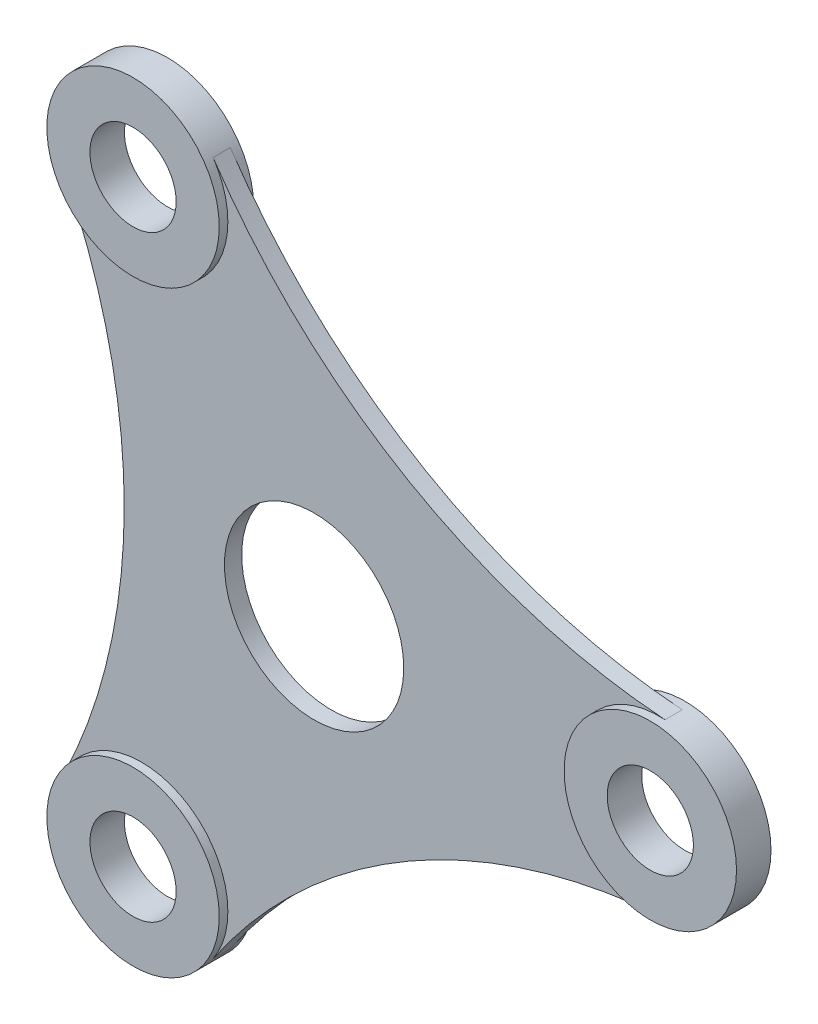
SolidWorks part; units mm, degrees
ref_plane "Front Plane" through (0, 0, 0) normal (0, 0, 1) x (1, 0, 0)
ref_plane "Top Plane" through (0, 0, 0) normal (0, 1, 0) x (1, 0, 0)
ref_plane "Right Plane" through (0, 0, 0) normal (1, 0, 0) x (0, 0, -1)
sketch "Sketch1" plane through (0, 0, 0) normal (0, 0, 1) x (1, 0, 0)
  circle A0 centre (0, 0) radius 200 construction
  circle A1 centre (0, 0) radius 52
  circle A2 centre (200, 0) radius 50
  circle A3 centre (-100, -173.2051) radius 50
  circle A4 centre (-100, 173.2051) radius 50
  arc A5 (-58.5788, 201.2101) -> (203.5424, 49.8744) centre (228.0562, 395.0049) ccw
  arc A6 (203.5424, -49.8744) -> (-58.5788, -201.2101) centre (228.0562, -395.0049) ccw
  arc A7 (-144.9637, -151.3358) -> (-144.9637, 151.3358) centre (-456.1123, 0) ccw
  circle A8 centre (-100, 173.2051) radius 25
  circle A9 centre (200, 0) radius 25
  circle A10 centre (-100, -173.2051) radius 25
  point P12 (0, 0)
  point P16 (0, 0)
  point P22 (0, 0)
  point P23 (0, 0)
  point P24 (0, 0)
  point P29 (0, 0)
  dimension "D1" = 400
  dimension "D2" = 104
  dimension "D3" = 100
  dimension "D5" = 346
  dimension "D7" = 50
  dimension "D4" = 3
  dimension "D6" = 3
  dimension "D8" = 3
extrude "Boss-Extrude1" add sketch "Sketch1" along normal mid plane 20 contours A4 A8 | A3 A10 | A2 A9 region at (235.5515, -33.116, 0) region at (-53.545, 187.4356, 0) region at (-124.2929, -215.2816, 0)
extrude "Boss-Extrude2" add sketch "Sketch1<3>" along normal mid plane 10 contours A7 A3 A6 A2 A5 A4 A1 region at (144.6765, 0, 0)
sketch "Sketch1<3>" plane through (0, 0, 0) normal (0, 0, 1) x (1, 0, 0) same geometry as "Sketch1"
